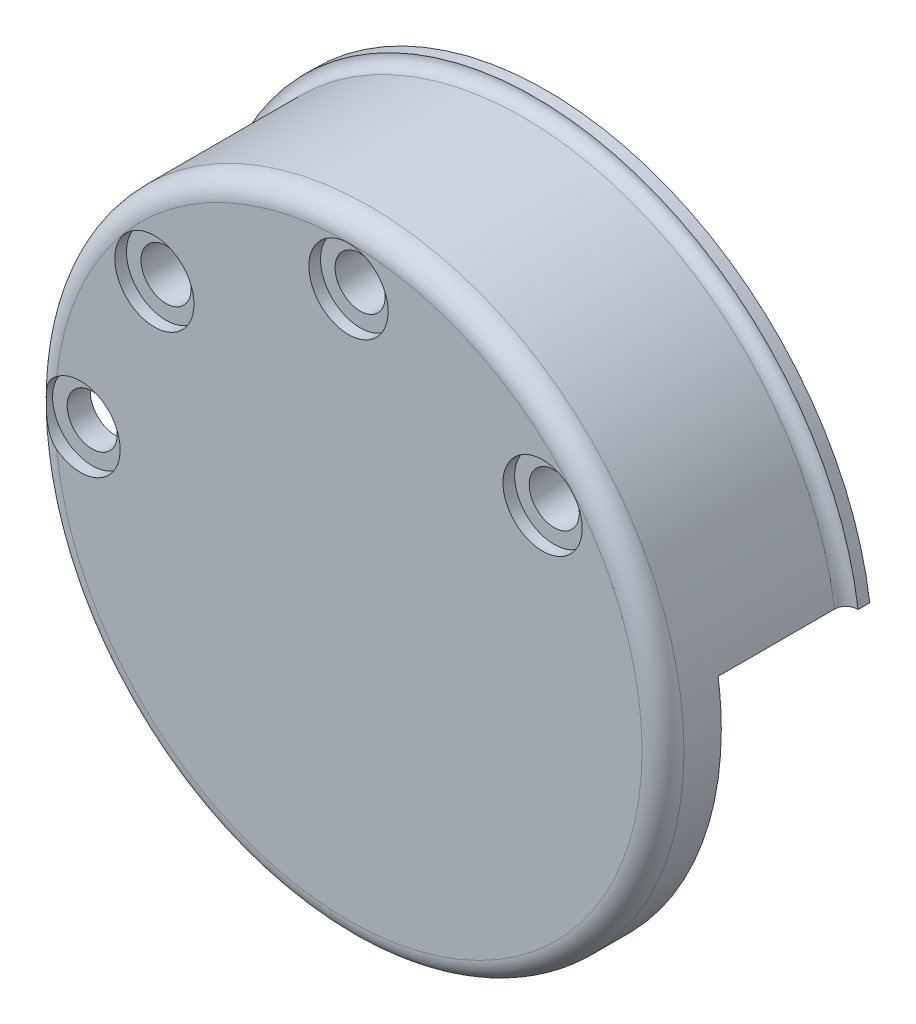
SolidWorks part; units mm, degrees
ref_plane "前视基准面" through (0, 0, 0) normal (0, 0, 1) x (1, 0, 0)
ref_plane "上视基准面" through (0, 0, 0) normal (0, 1, 0) x (1, 0, 0)
ref_plane "右视基准面" through (0, 0, 0) normal (1, 0, 0) x (0, 0, -1)
sketch "草图1" plane through (0, 0, 0) normal (0, 0, 1) x (1, 0, 0)
  line L0 (-28, 0) -> (28, 0)
  arc A1 (28, 0) -> (-28, 0) centre (0, 0) ccw
extrude "凸台-拉伸1" add sketch "草图1" along normal blind 15
sketch "草图2" plane through (0, 0, 15) normal (0, 0, 1) x (1, 0, 0)
  line L0 (0, 0) -> (-28, 0)
  line L1 (-28, 0) -> (28, 0) construction
  line L4 (0, 0) -> (15, 0)
  line L5 (15, 0) -> (28, 0)
  line L8 (-13.8242, 5.8215) -> (-27.3881, 5.8215)
  line L12 (14.4189, 4.1346) -> (19.4595, 4.0026)
  line L13 (27.7429, 3.7857) -> (19.4595, 4.0026)
  arc A0 (-28, 0) -> (-27.3881, 5.8215) centre (0, 0) cw
  arc A1 (-27.636, 4.5) -> (-27.636, -4.5) centre (0, 0) ccw construction
  arc A7 (14.0954, 5.1303) -> (-13.8242, 5.8215) centre (0, 0) ccw
  arc A8 (14.0954, 5.1303) -> (14.4189, 4.1346) centre (0, 0) cw
  arc A10 (28, 0) -> (-28, 0) centre (0, 0) ccw construction
  arc A12 (28, 0) -> (27.7429, 3.7857) centre (0, 0) ccw
extrude "切除-拉伸1" cut sketch "草图2" against normal blind 22
sketch "草图3" plane through (0, 0, 15) normal (0, 0, 1) x (1, 0, 0)
  circle A0 centre (0, 0) radius 28
extrude "凸台-拉伸2" add sketch "草图3" against normal blind 3 and the other way blind 2
sketch "草图4" plane through (0, 0, 12) normal (0, 0, -1) x (-1, 0, 0)
  line L1 (23, 5) -> (27.55, 5)
  line L2 (23, -5) -> (27.55, -5)
  arc A1 (-27.7429, 3.7857) -> (27.3881, 5.8215) centre (0, 0) ccw construction
  arc A2 (23, 5) -> (23, -5) centre (23, 0) ccw
  arc A3 (27.55, -5) -> (27.55, 5) centre (0, 0) ccw
extrude "切除-拉伸2" cut sketch "草图4" against normal blind 1
sketch "草图5" plane through (0, 0, 13) normal (0, 0, -1) x (-1, 0, 0)
  line L2 (23, 4.5) -> (27.636, 4.5)
  line L3 (23, -4.5) -> (27.636, -4.5)
  arc A2 (23, 4.5) -> (23, -4.5) centre (23, 0) ccw
  arc A3 (27.55, -5) -> (27.55, 5) centre (0, 0) ccw construction
  arc A8 (27.636, -4.5) -> (27.636, 4.5) centre (0, 0) ccw
extrude "切除-拉伸3" cut sketch "草图5" against normal blind 1
sketch "草图7" plane through (0, 0, 0) normal (0, 0, 1) x (1, 0, 0)
  circle A0 centre (-23, 0) radius 2.15
  circle A1 centre (16.6615, 13.9806) radius 2.15
  circle A2 centre (-16.6615, 13.9806) radius 2.15
  circle A3 centre (0, 21.75) radius 2.15
extrude "切除-拉伸4" cut sketch "草图7" along normal blind 18
sketch "草图8" plane through (0, 0, 0) normal (0, 0, 1) x (1, 0, 0)
  circle A0 centre (0, 0) radius 27
  circle A1 centre (0, 0) radius 28
extrude "切除-拉伸5" cut sketch "草图8" against normal blind 16 from surface starting at face at (-20.85, 0, 17)
fillet "圆角2" radius 1 1 edges at (1.0211, 26.9807, 1)
fillet "圆角3" radius 1.8 1 edges at (27, 0, 17)
sketch "草图9" plane through (0, 0, 17) normal (0, 0, 1) x (1, 0, 0)
  circle A0 centre (0, 21.75) radius 3.4
  circle A1 centre (16.6615, 13.9806) radius 3.4
  circle A2 centre (-16.6615, 13.9806) radius 3.4
  circle A3 centre (-23, 0) radius 3.4
extrude "切除-拉伸6" cut sketch "草图9" against normal blind 1
